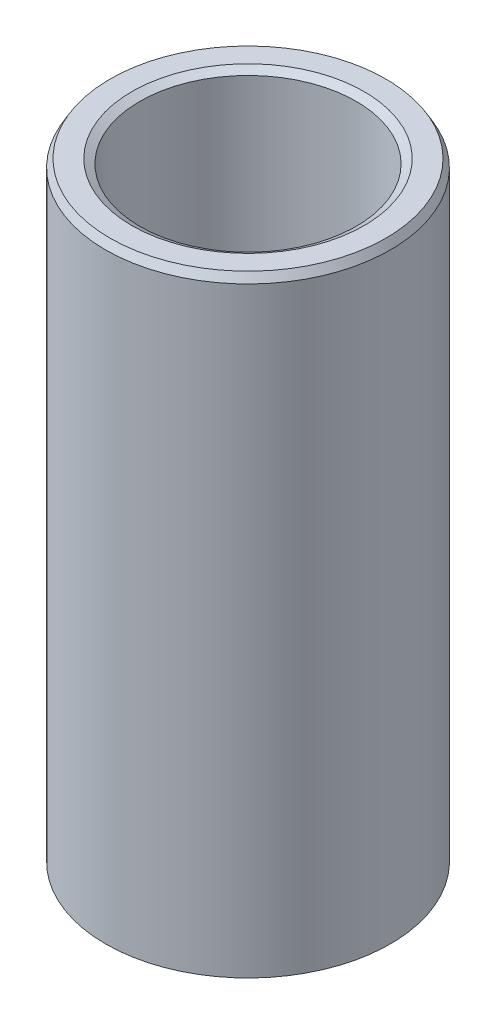
SolidWorks part; units mm, degrees
ref_plane "Front Plane" through (0, 0, 0) normal (0, 0, 1) x (1, 0, 0)
ref_plane "Top Plane" through (0, 0, 0) normal (0, 1, 0) x (1, 0, 0)
ref_plane "Right Plane" through (0, 0, 0) normal (1, 0, 0) x (0, 0, -1)
sketch "Sketch1" plane through (0, 0, 0) normal (0, 1, 0) x (1, 0, 0)
  circle A0 centre (0, 0) radius 42.5
  dimension "SLEEVE_OD" = 85
extrude "Boss-Extrude1" add sketch "Sketch1" along normal blind 183.0278
sketch "Sketch2" plane through (0, 0, 0) normal (0, 1, 0) x (1, 0, 0)
  circle A0 centre (0, 0) radius 32.3001
  dimension "BORE_D" = 64.6003
extrude "Cut-Extrude1" cut sketch "Sketch2" along normal through all
chamfer "Chamfer1" distance 2.3491 angle 30 4 edges at (0, 183.0278, 32.3001) (0, 0, 32.3001) (0, 0, 42.5) (0, 183.0278, 42.5) first distance on face at (0, 183.0278, 32.3001) first distance on face at (0, 0, 32.3001) first distance on face at (0, 183.0278, 42.5)
